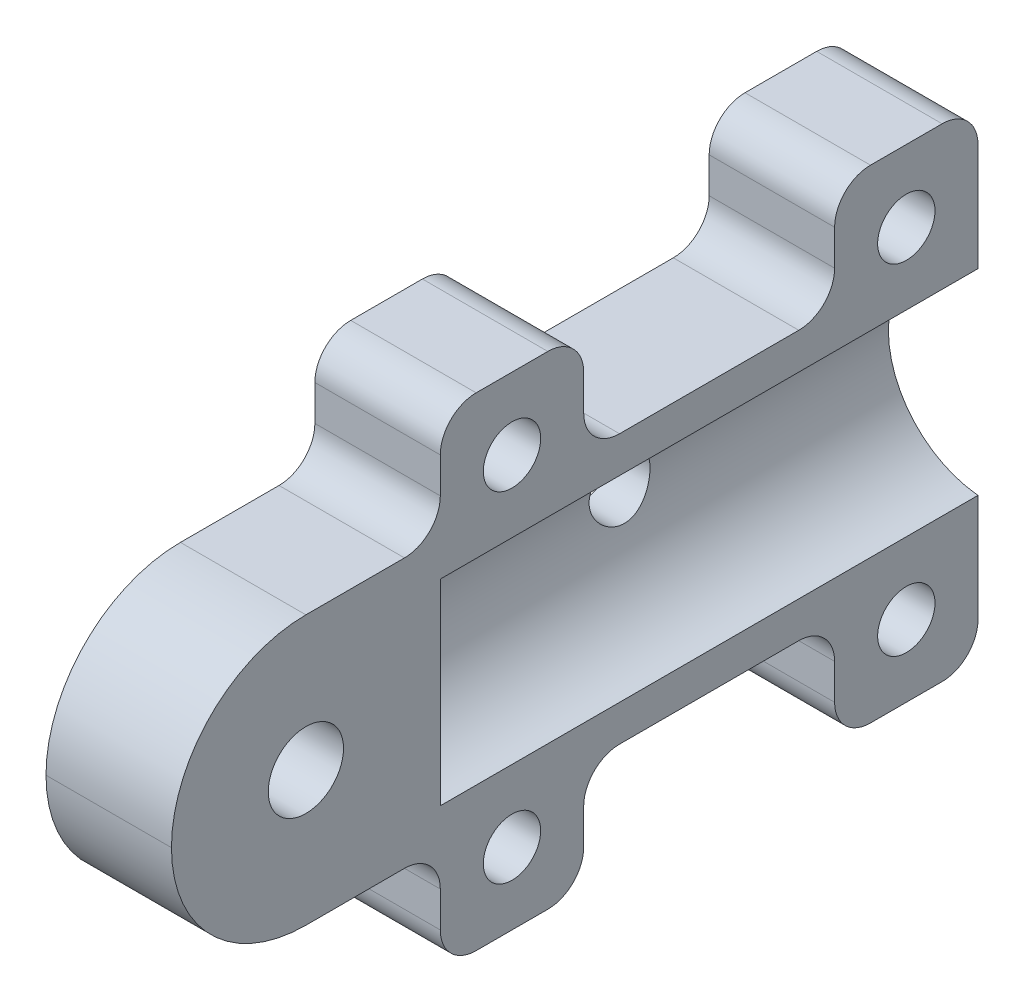
SolidWorks part; units mm, degrees
ref_plane "正面" through (0, 0, 0) normal (0, 0, 1) x (1, 0, 0)
ref_plane "平面" through (0, 0, 0) normal (0, 1, 0) x (1, 0, 0)
ref_plane "右側面" through (0, 0, 0) normal (1, 0, 0) x (0, 0, -1)
sketch "ｽｹｯﾁ1" plane through (0, 0, 0) normal (0, 0, 1) x (1, 0, 0)
  line L1 (-7.5, -7.5) -> (7.5, -7.5)
  line L2 (-7.5, -7.5) -> (-7.5, 7.5)
  line L3 (-7.5, 7.5) -> (7.5, 7.5)
  line L4 (7.5, -7.5) -> (7.5, 7.5)
  line L5 (-7.5, -7.5) -> (7.5, 7.5) construction
  line L6 (-7.5, 7.5) -> (7.5, -7.5) construction
  circle A0 centre (0, 0) radius 5.5
  dimension "D1" = 11
  dimension "D3" = 15
  dimension "D4" = 15
extrude "ﾎﾞｽ - 押し出し1" add sketch "ｽｹｯﾁ1" along normal blind 45
sketch "ｽｹｯﾁ5" plane through (0, 0, 45) normal (0, 0, 1) x (1, 0, 0)
  line L1 (7.5, -7.5) -> (-7.5, -7.5)
  line L2 (7.5, -7.5) -> (7.5, 7.5)
  line L3 (7.5, 7.5) -> (-7.5, 7.5)
  line L4 (-7.5, -7.5) -> (-7.5, 7.5)
  line L5 (7.5, -7.5) -> (-7.5, 7.5) construction
  line L6 (7.5, 7.5) -> (-7.5, -7.5) construction
  point P0 (0, 0)
extrude "ﾎﾞｽ - 押し出し3" add sketch "ｽｹｯﾁ5" against normal blind 15
fillet "ﾌｨﾚｯﾄ2" radius 7.5 2 edges at (0, -7.5, 45) (0, 7.5, 45)
sketch "ｽｹｯﾁ6" plane through (7.5, 0, 0) normal (1, 0, 0) x (0, 0, -1)
  circle A0 centre (-37.5, 0) radius 2.1
  dimension "D1" = 4.2
extrude "ｶｯﾄ - 押し出し1" cut sketch "ｽｹｯﾁ6" against normal through all
sketch "ｽｹｯﾁ7" plane through (7.5, 0, 0) normal (1, 0, 0) x (0, 0, -1)
  line L10 (-37.5, -9.5) -> (2, -9.5)
  line L11 (2, -9.5) -> (2, 9.5)
  line L12 (2, 9.5) -> (-37.5, 9.5)
  line L13 (-37.5, -9.5) -> (2, -9.5)
  line L14 (2, -9.5) -> (2, 9.5)
  line L15 (2, 9.5) -> (-37.5, 9.5)
  arc A6 (-37.5, 9.5) -> (-47, 0) centre (-37.5, 0) ccw
  arc A7 (-47, 0) -> (-37.5, -9.5) centre (-37.5, 0) ccw
  arc A8 (-37.5, 9.5) -> (-47, 0) centre (-37.5, 0) ccw
  arc A9 (-47, 0) -> (-37.5, -9.5) centre (-37.5, 0) ccw
  dimension "D1" = 2
extrude "ｶｯﾄ - 押し出し2" cut sketch "ｽｹｯﾁ7" against normal blind 8
sketch "ｽｹｯﾁ9" plane through (-0.5, 0, 0) normal (1, 0, 0) x (0, 0, -1)
  line L0 (-30, -5.4772) -> (0, -5.4772) construction
  line L1 (0, -5.4772) -> (-8, -5.4772)
  line L2 (0, -5.4772) -> (0, -13.4772)
  line L3 (0, -13.4772) -> (-8, -13.4772)
  line L4 (-8, -5.4772) -> (-8, -13.4772)
  line L5 (-30, 5.4772) -> (-22, 5.4772)
  line L6 (-30, 5.4772) -> (-30, 13.4772)
  line L7 (-30, 13.4772) -> (-22, 13.4772)
  line L8 (-22, 5.4772) -> (-22, 13.4772)
  line L9 (0, 5.4772) -> (-8, 5.4772)
  line L10 (0, 5.4772) -> (0, 13.4772)
  line L11 (0, 13.4772) -> (-8, 13.4772)
  line L12 (-8, 5.4772) -> (-8, 13.4772)
  line L13 (-22, -5.4772) -> (-30, -5.4772)
  line L14 (-22, -5.4772) -> (-22, -13.4772)
  line L15 (-22, -13.4772) -> (-30, -13.4772)
  line L16 (-30, -5.4772) -> (-30, -13.4772)
  circle A0 centre (-4, -9.4772) radius 1.6
  circle A1 centre (-26, 9.4772) radius 1.6
  circle A2 centre (-26, -9.4772) radius 1.6
  circle A3 centre (-4, 9.4772) radius 1.6
  dimension "D7" = 4
  dimension "D8" = 4
  dimension "D9" = 3.2
  dimension "D10" = 4
  dimension "D11" = 4
  dimension "D12" = 3.2
  dimension "D13" = 3.2
  dimension "D14" = 4
  dimension "D16" = 4
  dimension "D18" = 3.2
  dimension "D1" = 8
  dimension "D2" = 8
  dimension "D3" = 8
  dimension "D4" = 8
  dimension "D5" = 8
  dimension "D6" = 8
  dimension "D15" = 4
  dimension "D17" = 4
extrude "ﾎﾞｽ - 押し出し4" add sketch "ｽｹｯﾁ9" against normal blind 7
fillet "ﾌｨﾚｯﾄ3" radius 2 14 edges at (-4, 7.5, 30) (-4, 13.4772, 30) (-4, 13.4772, 22) (-4, 7.5, 22) (-4, 7.5, 8) (-4, 13.4772, 8) (-4, 13.4772, 0) (-4, -13.4772, 0) (-4, -13.4772, 8) (-4, -7.5, 8) (-4, -7.5, 22) (-4, -13.4772, 22) (-4, -7.5, 30) (-4, -13.4772, 30)
sketch "ｽｹｯﾁ11" plane through (-7.5, 0, 0) normal (-1, 0, 0) x (0, 0, 1)
  circle A0 centre (4, 9.4772) radius 3.2
  circle A1 centre (26, 9.4772) radius 3.2
  circle A2 centre (26, -9.4772) radius 3.2
  circle A3 centre (4, -9.4772) radius 3.2
  dimension "D1" = 6.4
  dimension "D2" = 6.4
  dimension "D3" = 6.4
  dimension "D4" = 6.4
extrude "ｶｯﾄ - 押し出し3" cut sketch "ｽｹｯﾁ11" against normal blind 3.75
sketch "ｽｹｯﾁ12" plane through (-7.5, 0, 0) normal (-1, 0, 0) x (0, 0, 1)
  line L0 (0, 11.4772) -> (0, -11.4772) construction
  circle A0 centre (15, 0) radius 1.7
  dimension "D1" = 15
  dimension "D2" = 3.4
extrude "ｶｯﾄ - 押し出し4" cut sketch "ｽｹｯﾁ12" against normal blind 10
